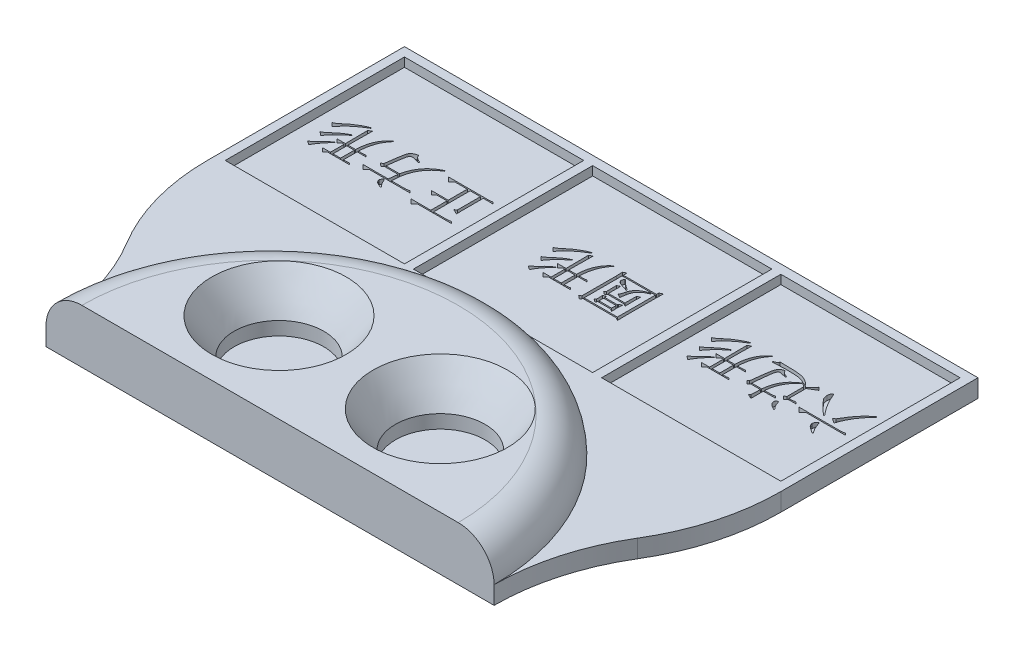
SolidWorks part; units mm, degrees
ref_plane "前视基准面" through (0, 0, 0) normal (0, 0, 1) x (1, 0, 0)
ref_plane "上视基准面" through (0, 0, 0) normal (0, 1, 0) x (1, 0, 0)
ref_plane "右视基准面" through (0, 0, 0) normal (1, 0, 0) x (0, 0, -1)
other "Configuration Table"
sketch "草图1" plane through (0, 0, 0) normal (0, 1, 0) x (1, 0, 0)
  line L6 (0, -20) -> (50, -20)
  line L23 (0, -20) -> (-50, -20)
  line L25 (-1, 70) -> (-1, 30)
  line L26 (1, 70) -> (41, 70)
  line L27 (43, 52) -> (85, 52)
  line L32 (1, 30) -> (41, 30)
  line L36 (1, 70) -> (1, 30)
  line L37 (-41, 30) -> (-1, 30)
  line L38 (-41, 70) -> (-1, 70)
  line L39 (-43, 72) -> (43, 72)
  line L40 (-43, 50) -> (-43, 10)
  line L41 (-41, 70) -> (-41, 30)
  line L42 (-43, 10) -> (-83, 10)
  line L43 (-83, 10) -> (-83, 50)
  line L44 (-83, 50) -> (-43, 50)
  line L45 (41, 70) -> (41, 30)
  line L46 (85, 8) -> (85, 52)
  line L48 (43, 10) -> (83, 10)
  line L49 (43, 52) -> (43, 72)
  line L50 (43, 50) -> (43, 10)
  line L51 (83, 10) -> (83, 50)
  line L52 (43, 50) -> (83, 50)
  line L61 (50, -20) -> (57, -20)
  line L63 (-50, -20) -> (-57, -20)
  line L64 (-85, 50) -> (-85, 8)
  line L65 (-85, 50) -> (-85, 52)
  line L66 (-85, 52) -> (-43, 52)
  line L67 (-43, 52) -> (-43, 72)
  circle A0 centre (18, 0) radius 10
  circle A1 centre (-18, 0) radius 10
  arc A3 (85, 8) -> (57, -20) centre (57, 8) cw
  arc A4 (-57, -20) -> (-85, 8) centre (-57, 8) cw
extrude "凸台-拉伸1" add sketch "草图1" along normal blind 2
sketch "草图2" plane through (0, 0, 0) normal (0, -1, 0) x (1, 0, 0)
  line L0 (-85, -8) -> (-85, -52)
  line L1 (-85, -52) -> (-43, -52)
  line L2 (-43, -52) -> (-43, -72)
  line L3 (-43, -72) -> (43, -72)
  line L4 (43, -72) -> (43, -52)
  line L5 (43, -52) -> (85, -52)
  line L6 (85, -52) -> (85, -8)
  line L7 (-57, 20) -> (57, 20)
  arc A0 (-85, -8) -> (-57, 20) centre (-57, -8) cw
  arc A1 (57, 20) -> (85, -8) centre (57, -8) cw
  circle A2 centre (-18, 0) radius 10
  circle A3 centre (18, 0) radius 10
extrude "凸台-拉伸2" add sketch "草图2" along normal blind 2
sketch "草图4" plane through (0, 2, 0) normal (0, 1, 0) x (1, 0, 0)
  line L0 (0, -20) -> (-50, -20)
  line L1 (-57, -20) -> (57, -20) construction
  line L2 (-50, -20) -> (50, -20)
  arc A0 (-50, -20) -> (50, -20) centre (0, -20) cw
  circle A3 centre (-18, 0) radius 15
  circle A4 centre (18, 0) radius 15
  line M14 (-57, -20) -> (57, -20)
extrude "凸台-拉伸3" add sketch "草图4" along normal blind 8 contours A0 A4 A3 M14 region at (0, 2, -1.9073)
loft "切除-放样1" cut section edge at (-18, 10, 15) section edge at (-18, 2, 10) end constraint default connector at (-3.9419, 10, -5.2315) connector at (-9.8366, 2, -5.7757)
sketch "草图5" plane through (0, 2, 0) normal (0, 1, 0) x (1, 0, 0)
  circle A0 centre (-18, 0) radius 10
sketch "草图6" plane through (0, 10, 0) normal (0, 1, 0) x (1, 0, 0)
  circle A0 centre (-18, 0) radius 15
sketch "草图7" plane through (0, 10, 0) normal (0, 1, 0) x (1, 0, 0)
  circle A0 centre (-18, 0) radius 15
  circle A1 centre (-18, 0) radius 10
extrude "凸台-拉伸4" add sketch "草图7" against normal blind 8 contours A0 | A1
loft "切除-放样2" cut profiles "草图6", "草图5" connector at (-3.6249, 10, -4.2843) connector at (-10.0221, 2, -6.0293)
sketch "草图9" plane through (0, 2, 0) normal (0, 1, 0) x (1, 0, 0)
  circle A0 centre (18, 0) radius 10
sketch "草图10" plane through (0, 10, 0) normal (0, 1, 0) x (1, 0, 0)
  circle A0 centre (18, 0) radius 15
sketch "草图11" plane through (0, 10, 0) normal (0, 1, 0) x (1, 0, 0)
  circle A0 centre (18, 0) radius 10
  circle A1 centre (18, 0) radius 15
extrude "凸台-拉伸5" add sketch "草图11" against normal blind 8
loft "切除-放样3" cut profiles "草图10", "草图9" connector at (32.657, 10, -3.1893) connector at (26.6644, 2, -4.9927)
fillet "圆角1" radius 8 1 edges at (0, 10, -30)
sketch "草图20" plane through (0, 2, 0) normal (0, 1, 0) x (1, 0, 0)
  circle A0 centre (-18, 0) radius 10
  circle A1 centre (18, 0) radius 10
extrude "凸台-拉伸7" add sketch "草图20" against normal blind 1
sketch "草图21" plane through (0, 2, 0) normal (0, 1, 0) x (1, 0, 0)
  line L0 (-42, -20) -> (42, -20) construction
  line L1 (-50, -20) -> (-42, -20) construction
  line L2 (-50, -20) -> (-103.4635, -20)
  line L3 (-103.4635, -20) -> (-103.4635, 85.0865)
  line L4 (50, -20) -> (103.2152, -20)
  line L5 (103.2152, -20) -> (103.2152, 85.0865)
  line L6 (103.2152, 85.0865) -> (-103.4635, 85.0865)
  arc A0 (-50, -20) -> (50, -20) centre (0, -20) cw
  arc A1 (50, -20) -> (-50, -20) centre (0, -20) ccw construction
extrude "切除-拉伸2" cut sketch "草图21" against normal blind 4
sketch "草图22" plane through (0, -2, 0) normal (0, -1, 0) x (1, 0, 0)
  line L22 (-64, -30) -> (-64, -74)
  line L23 (-64, -74) -> (0, -74)
  line L24 (64, -30) -> (64, -74)
  line L25 (64, -74) -> (0, -74)
  line L28 (50, 20) -> (-50, 20) construction
  arc A1 (-50, 20) -> (-57, -5) centre (-98.1429, 20) cw
  arc A2 (-64, -30) -> (-57, -5) centre (-15.8571, -30) cw
  arc A3 (64, -30) -> (57, -5) centre (15.8571, -30) ccw
  arc A4 (57, -5) -> (50, 20) centre (98.1429, 20) cw
  arc A5 (-50, 20) -> (50, 20) centre (0, 20) ccw
extrude "凸台-拉伸8" add sketch "草图22" against normal blind 4
sketch "草图23" plane through (0, 2, 0) normal (0, 1, 0) x (1, 0, 0)
  line L0 (-22, 72) -> (-20, 72)
  line L1 (-64, 74) -> (-62, 74)
  line L2 (-64, 74) -> (-64, 72)
  line L3 (-64, 72) -> (-62, 72)
  line L4 (-62, 74) -> (-62, 72)
  line L9 (-62, 72) -> (-22, 72)
  line L10 (-62, 72) -> (-62, 32)
  line L11 (-62, 32) -> (-22, 32)
  line L12 (-22, 72) -> (-22, 32)
  line L17 (20, 72) -> (22, 72)
  line L18 (-20, 72) -> (20, 72)
  line L19 (-20, 72) -> (-20, 32)
  line L20 (-20, 32) -> (20, 32)
  line L21 (20, 72) -> (20, 32)
  line L23 (22, 72) -> (62, 72)
  line L24 (22, 72) -> (22, 32)
  line L25 (22, 32) -> (62, 32)
  line L26 (62, 72) -> (62, 32)
extrude "切除-拉伸3" cut sketch "草图23" against normal blind 2 contours L12 L9 L10 L11 | L21 L18 L19 L20 | L26 L23 L24 L25 region at (42, 2, -52) region at (0, 2, -52) region at (-42, 2, -52)
sketch "草图24" plane through (0, 0, 0) normal (0, 1, 0) x (1, 0, 0)
  text T0 "<r180>形方正" font "宋体" height in points 26
  text T1 "<r180>形圆" font "宋体" height in points 26
  text T2 "<r180>形边六" font "宋体" height in points 26
extrude "切除-拉伸4" cut sketch "草图24" against normal blind 1
sketch "草图28" plane through (0, -2, 0) normal (0, -1, 0) x (1, 0, 0)
  circle A0 centre (-18, 0) radius 10
  circle A1 centre (18, 0) radius 10
extrude "凸台-拉伸10" add sketch "草图28" against normal blind 4
sketch "草图29" plane through (0, 2, 0) normal (0, 1, 0) x (1, 0, 0)
  circle A0 centre (-18, 0) radius 10
  circle A1 centre (18, 0) radius 10
extrude "切除-拉伸5" cut sketch "草图29" against normal blind 3
